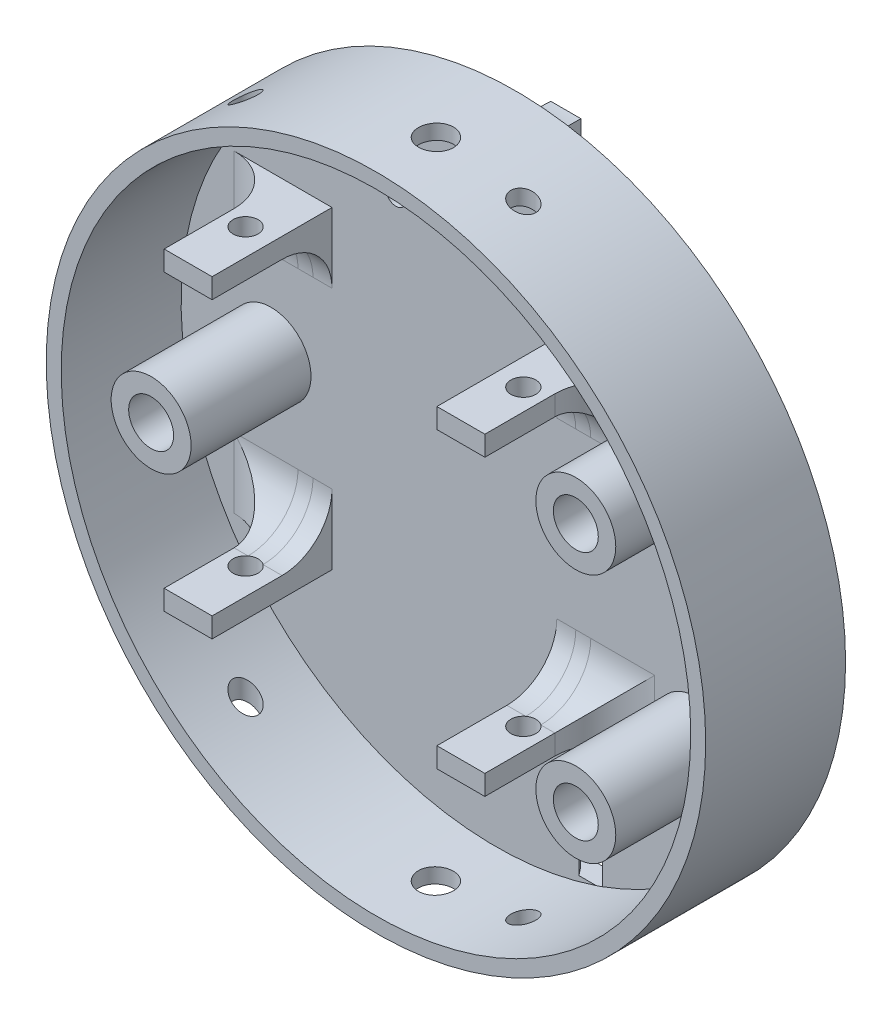
SolidWorks part; units mm, degrees
ref_plane "Alzado" through (0, 0, 0) normal (0, 0, 1) x (1, 0, 0)
ref_plane "Planta" through (0, 0, 0) normal (0, 1, 0) x (1, 0, 0)
ref_plane "Vista lateral" through (0, 0, 0) normal (1, 0, 0) x (0, 0, -1)
sketch "Croquis1" plane through (0, 0, 0) normal (0, 0, 1) x (1, 0, 0)
  line L0 (10, 20) -> (-10, 20) construction
  circle A0 centre (0, 0) radius 33
  circle A3 centre (0, 20) radius 1
  circle A4 centre (10, 20) radius 1
  circle A5 centre (-10, 20) radius 1
  point P9 (0, 20)
  dimension "D1" = 66
  dimension "D7" = 2
  dimension "D5" = 20
  dimension "D6" = 20
extrude "Saliente-Extruir1" add sketch "Croquis1" along normal blind 2
sketch "Croquis2" plane through (0, 0, 2) normal (0, 0, 1) x (1, 0, 0)
  line L0 (-21.2, -15.7) -> (-16.4, -15.7)
  line L1 (10.9, -15.7) -> (6.1, -15.7)
  line L2 (-21.2, -15.7) -> (-21.2, -13.7)
  line L3 (-21.2, -13.7) -> (-16.4, -13.7)
  line L4 (-16.4, -13.7) -> (-16.4, -15.7)
  line L5 (6.1, -15.7) -> (6.1, -13.7)
  line L6 (6.1, -13.7) -> (10.9, -13.7)
  line L7 (10.9, -13.7) -> (10.9, -15.7)
  line L8 (6.1, -15.7) -> (10.9, -15.7)
  line L9 (0, 0) -> (12.8027, 0) construction
  line L10 (10.9, 13.7) -> (10.9, 15.7)
  line L11 (10.9, 15.7) -> (6.1, 15.7)
  line L12 (6.1, 13.7) -> (10.9, 13.7)
  line L13 (6.1, 15.7) -> (6.1, 13.7)
  line L14 (-16.4, 13.7) -> (-16.4, 15.7)
  line L15 (-21.2, 15.7) -> (-16.4, 15.7)
  line L16 (-21.2, 15.7) -> (-21.2, 13.7)
  line L17 (-21.2, 13.7) -> (-16.4, 13.7)
  point P2 (0, -15.7)
  point P3 (-16.4, -15.7)
  point P13 (8.5, -15.7)
  point P16 (8.5, 15.7)
  dimension "D1" = 32.1
  dimension "D2" = 10.9
  dimension "D3" = 15.7
  dimension "D4" = 4.8
  dimension "D5" = 4.8
  dimension "D6" = 2
  dimension "D7" = 2
extrude "Saliente-Extruir2" add sketch "Croquis2" along normal blind 12 contours L7 L6 L5 L1 | L4 L3 L2 L0 | L16 L17 L14 L15 | L11 L13 L12 L10 region at (-18.8, -14.7, 2) region at (8.5, -14.7, 2) region at (8.5, 14.7, 2) region at (-18.8, 14.7, 2)
sketch "Croquis3" plane through (0, -15.7, 0) normal (0, -1, 0) x (1, 0, 0)
  line L0 (-21.2, 14) -> (-21.2, 2) construction
  line L3 (10.9, 14) -> (10.9, 2) construction
  line L6 (-21.2, 2) -> (-16.4, 2) construction
  circle A0 centre (-19.05, 8) radius 1.25
  circle A1 centre (8.75, 8) radius 1.25
  dimension "D1" = 2.5
  dimension "D2" = 2.15
  dimension "D3" = 2.15
  dimension "D4" = 6
extrude "Cortar-Extruir1" cut sketch "Croquis3" against normal up to surface (31.4 mm away) up to face at (8.5, 15.7, 8)
ref_plane "Plano1" through (0, -33, 0) normal (0, -1, 0) x (-1, 0, 0)
ref_plane "Plano2" through (0, -29.85, 0) normal (0, -1, 0) x (-1, 0, 0)
sketch "Croquis5" plane through (0, -29.85, 0) normal (0, -1, 0) x (-1, 0, 0)
  line L0 (-8.75, -8) -> (19.05, -8) construction
  line L1 (0, 0) -> (0, -8) construction
  line L2 (-33, -2) -> (33, -2) construction
  line L3 (-10.68, -2) -> (-8.3104, -2)
  line L4 (33, 0) -> (-33, 0) construction
  line L5 (9.277, 0) -> (6.408, 0)
  line L6 (8.3104, -2) -> (10.68, -2)
  line L7 (-6.408, 0) -> (-9.277, 0)
  arc A0 (-9.277, 0) -> (-10.68, -2) centre (0, -8) ccw
  arc A1 (-6.408, 0) -> (-8.3104, -2) centre (0, -8) ccw
  arc A2 (10.68, -2) -> (9.277, 0) centre (0, -8) ccw
  arc A3 (8.3104, -2) -> (6.408, 0) centre (0, -8) ccw
  dimension "D1" = 24.5
  dimension "D2" = 20.5
extrude "Cortar-Extruir3" cut sketch "Croquis5" against normal blind 5
mirror "Simetría1" about plane through (0, 0, 0) normal (0, 1, 0) of "Cortar-Extruir3"
sketch "Croquis6" plane through (0, 0, 0) normal (0, 0, -1) x (-1, 0, 0)
  circle A0 centre (-20, 12.5) radius 2.25
  circle A1 centre (-20, -12.5) radius 2.25
  circle A2 centre (22.5, 0) radius 2.25
  dimension "D1" = 4.5
  dimension "D2" = 4.5
  dimension "D3" = 4.5
  dimension "D6" = 25
  dimension "D7" = 12.5
  dimension "D4" = 22.5
  dimension "D5" = 20
extrude "Cortar-Extruir4" cut sketch "Croquis6" against normal blind 2.5
sketch "Croquis7" plane through (0, 0, 2) normal (0, 0, 1) x (1, 0, 0)
  circle A2 centre (0, 0) radius 33 construction
  circle A9 centre (0, 0) radius 33
  circle A11 centre (0, 0) radius 31.5
  dimension "D1" = 1.5
extrude "Saliente-Extruir3" add sketch "Croquis7" along normal blind 12
ref_plane "Plano3" through (0, -33, 0) normal (0, -1, 0) x (-1, 0, 0)
sketch "Croquis8" plane through (0, -33, 0) normal (0, -1, 0) x (-1, 0, 0)
  circle A0 centre (-8.75, -8) radius 1.25 construction
  circle A1 centre (-8.75, -8) radius 1.25
  circle A2 centre (19.05, -8) radius 1.25 construction
  circle A3 centre (19.05, -8) radius 1.25
  circle A4 centre (0, -8) radius 1.75
  dimension "D1" = 3.5
extrude "Cortar-Extruir5" cut sketch "Croquis8" against normal blind 70
sketch "Sketch1" plane through (0, 0, 0) normal (0, 0, -1) x (-1, 0, 0)
  line L0 (6.408, 24.85) -> (6.408, 29.85) construction
  line L1 (-1.502, 28.85) -> (1.498, 28.85)
  line L2 (-1.502, 28.85) -> (-1.502, 25.85)
  line L3 (-1.502, 25.85) -> (1.498, 25.85)
  line L4 (1.498, 28.85) -> (1.498, 25.85)
  line L5 (-1.502, 28.85) -> (1.498, 25.85) construction
  line L6 (-1.502, 25.85) -> (1.498, 28.85) construction
  line L7 (0, 0) -> (-11.4103, 0) construction
  line L8 (-1.502, -25.85) -> (1.498, -28.85) construction
  line L9 (-1.502, -28.85) -> (1.498, -25.85) construction
  line L10 (1.498, -28.85) -> (1.498, -25.85)
  line L11 (-1.502, -25.85) -> (1.498, -25.85)
  line L12 (-1.502, -28.85) -> (-1.502, -25.85)
  line L13 (-1.502, -28.85) -> (1.498, -28.85)
  line L14 (-6.408, -24.85) -> (-6.408, -29.85) construction
  point P0 (-0.002, 27.35)
  point P8 (6.408, 27.35)
  point P15 (-0.002, -27.35)
  dimension "D1" = 4.91
  dimension "D2" = 3
  dimension "D3" = 3
  dimension "D4" = 4.906
extrude "Boss-Extrude1" add sketch "Sketch1" along normal blind 5
fillet "Fillet1" radius 2 6 edges at (1.502, 27.35, 0) (-1.498, -27.35, 0) (0.002, 25.85, 0) (0.002, 28.85, 0) (0.002, -25.85, 0) (0.002, -28.85, 0) second distance 5 first distance on face at (0.002, 27.35, 0)
sketch "Sketch2" plane through (0, 0, 2) normal (0, 0, 1) x (1, 0, 0)
  line L1 (-10.68, -24.85) -> (-5.6668, -24.85)
  line L2 (-10.68, -24.85) -> (-10.68, -30.4984)
  line L3 (-10.68, -30.4984) -> (-5.6668, -30.4984)
  line L4 (-5.6668, -24.85) -> (-5.6668, -30.4984)
  line L5 (10.68, 24.85) -> (5.4941, 24.85)
  line L6 (10.68, 24.85) -> (10.68, 30.3368)
  line L7 (10.68, 30.3368) -> (5.4941, 30.3368)
  line L8 (5.4941, 24.85) -> (5.4941, 30.3368)
extrude "Tapon" add sketch "Sketch2" against normal up to surface (2 mm away) up to face at (1.002, 25.6, 0)
fillet "Fillet4" radius 5 8 edges at (-21.2, 14.7, 2) (-21.2, -14.7, 2) (-18.8, -13.7, 2) (-18.8, 13.7, 2) (10.9, 14.7, 2) (8.5, 13.7, 2) (8.5, -13.7, 2) (10.9, -14.7, 2)
sketch "Croquis9" plane through (0, 0, 2) normal (0, 0, 1) x (1, 0, 0)
  circle A0 centre (20, -12.5) radius 2.25 construction
  circle A1 centre (20, -12.5) radius 2.25
  circle A2 centre (-22.5, 0) radius 2.25 construction
  circle A3 centre (-22.5, 0) radius 2.25
  circle A4 centre (20, 12.5) radius 2.25 construction
  circle A5 centre (20, 12.5) radius 2.25
  circle A6 centre (-22.5, 0) radius 4
  circle A7 centre (20, -12.5) radius 4
  circle A8 centre (20, 12.5) radius 4
  dimension "D1" = 8
extrude "Saliente-Extruir4" add sketch "Croquis9" along normal up to surface (12 mm away) up to face at (33, 0, 14)
sketch "Sketch3" plane through (0, 0, 0) normal (0, 0, -1) x (-1, 0, 0)
  line L1 (5, -5) -> (-5, -5)
  line L2 (5, -5) -> (5, 5)
  line L3 (5, 5) -> (-5, 5)
  line L4 (-5, -5) -> (-5, 5)
  line L5 (5, -5) -> (-5, 5) construction
  line L6 (5, 5) -> (-5, -5) construction
  point P0 (0, 0)
  dimension "D1" = 10
  dimension "D2" = 10
extrude "Cut-Extrude1" cut sketch "Sketch3" against normal blind 0.5
equation "\"D2@Croquis6\"=\"D1@Croquis6\""
equation "\"D3@Croquis6\"=\"D1@Croquis6\""
equation "\"D7@Croquis6\"=\"D6@Croquis6\"/2"
